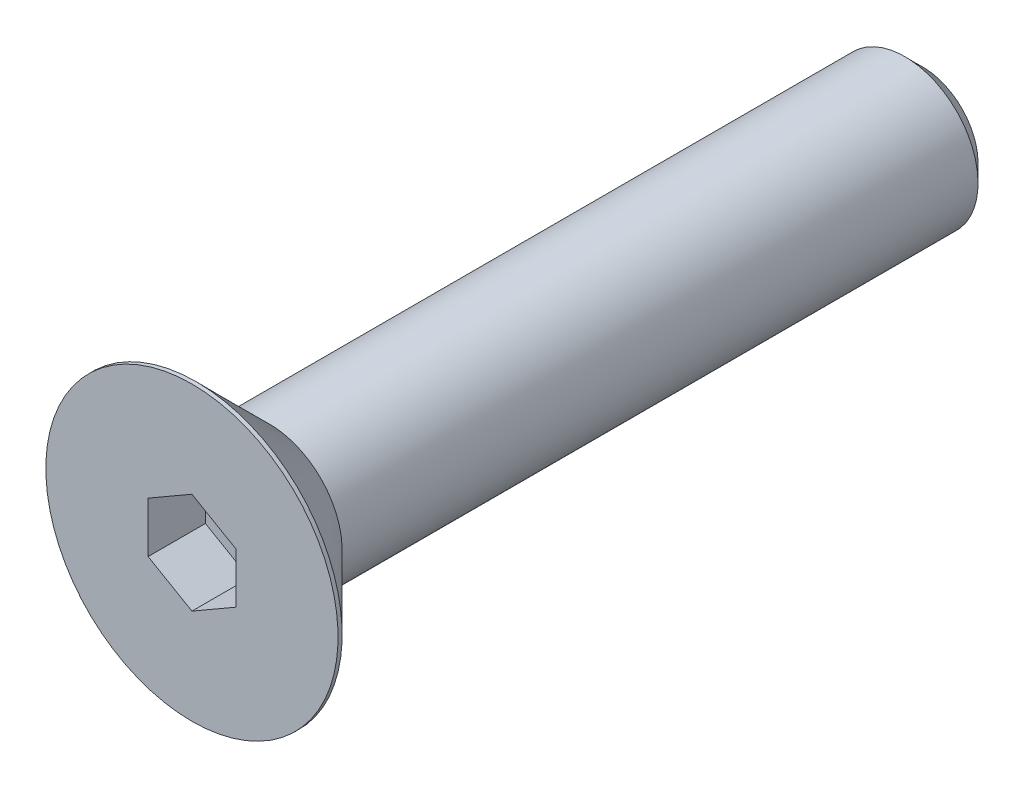
SolidWorks part; units mm, degrees
material "Chrome Stainless Steel"
ref_plane "Front" through (0, 0, 0) normal (0, 0, 1) x (1, 0, 0)
ref_plane "Top" through (0, 0, 0) normal (0, 1, 0) x (1, 0, 0)
ref_plane "Right" through (0, 0, 0) normal (1, 0, 0) x (0, 0, -1)
sketch "Sketch11" plane through (0, 0, 0) normal (1, 0, 0) x (0, 0, -1)
  line L0 (-12.5, 5) -> (12.5, 5) construction
  line L5 (-12.5, 5) -> (-12.5, -5) construction
  line L6 (12.5, 2.5) -> (12.5, -2.5) construction
  line L7 (-12.49, 1.5) -> (-12.49, -1.5) construction
  line L8 (12.45, 2.5866) -> (13.25, 2.5866) construction
  line L9 (13.25, 2.5866) -> (12.85, 1.8938) construction
  line L10 (12.85, 1.8938) -> (12.45, 2.5866) construction
  line L11 (12.8, 1.9804) -> (12.9, 1.9804) construction
  line L12 (12.85, 1.9804) -> (12.85, 1.8938) construction
  line L13 (12.475, 2.5433) -> (13.225, 2.5433) construction
  line L14 (12.85, 2.5866) -> (12.85, 2.5) construction
  line L15 (12.5, 2.5) -> (13.2, 2.5) construction
  line L17 (-12.36, 5) -> (-7.36, 0) construction
  line L18 (-7.36, 0) -> (-12.36, -5) construction
  point P3 (-9.7, 5)
  point P8 (0, 5)
  point P21 (12.85, 2.5433)
  point P26 (-12.5, 0)
  point P28 (-12.49, 0)
  point P29 (12.5, 0)
  dimension "Length" = 25
  dimension "Head Diameter" = 10
  dimension "Thread Major Diameter" = 5
  dimension "Head Height" = 2.8
  dimension "Drive Size" = 3
  dimension "Thread Pitch" = 0.8
  dimension "D1" = 0.1
  dimension "D2" = 0.01
  dimension "D3" = 0.14
  dimension "Countersink Angle" = 90
sketch "Sketch1" plane through (0, 0, 0) normal (1, 0, 0) x (0, 0, -1)
  line L2 (-9.7, 2.5) -> (12.5, 2.5)
  line L3 (12.5, 2.5) -> (12.5, 0)
  line L4 (-10.54, 2.5) -> (-10.54, 0)
  line L5 (-9.7, 2.5) -> (-10.54, 2.5)
  line L6 (-12.5, 5) -> (-12.5, -5) construction
  line L7 (12.5, 2.5) -> (12.5, -2.5) construction
  line L8 (-10.54, 0) -> (12.5, 0)
  dimension "D1" = 1.96
revolve "Revolve1" add sketch "Sketch1" angle 360 mid plane about L8
chamfer "Chamfer1" distance 0.6 angle 45 1 edges at (0, -2.5, -12.5)
sketch "Sketch7" plane through (0, 0, 0) normal (1, 0, 0) x (0, 0, -1)
  line L2 (-12.5, 5) -> (-12.36, 5)
  line L5 (-9.7, 2.34) -> (-9.7, 0)
  line L6 (-12.5, 5) -> (-12.5, 0)
  line L8 (-12.5, 5) -> (-12.5, -5) construction
  line L9 (-12.5, 0) -> (-9.7, 0)
  line L12 (-12.36, 5) -> (-9.7, 2.34)
  line L13 (-12.36, 5) -> (-7.36, 0) construction
revolve "Revolve2" add sketch "Sketch7" angle 360 mid plane about L9 region at (0, 1.9545, 11.2736)
ref_plane "Plane1" through (0, 0, 9.7) normal (0, 0, 1) x (1, 0, 0)
sketch "Sketch5" plane through (0, 0, 12.5) normal (0, 0, 1) x (1, 0, 0)
  line L1 (1.5, -0.866) -> (1.5, 0.866)
  line L2 (1.5, 0.866) -> (0, 1.7321)
  line L3 (0, 1.7321) -> (-1.5, 0.866)
  line L4 (-1.5, 0.866) -> (-1.5, -0.866)
  line L5 (-1.5, -0.866) -> (0, -1.7321)
  line L6 (0, -1.7321) -> (1.5, -0.866)
  circle A0 centre (0, 0) radius 1.5 construction
extrude "Cut-Extrude2" cut sketch "Sketch5" against normal blind 1.96
sketch "Sketch6" plane through (0, 0, 12.5) normal (0, 0, -1) x (-1, 0, 0)
  circle A0 centre (0, 0) radius 1.7321
extrude "Cut-Extrude3" [suppressed] cut sketch "Sketch6" along normal blind 1.96 draft 45
sketch "Sketch12" [suppressed] plane through (0, 0, -12.5) normal (0, 0, -1) x (-1, 0, 0)
  circle A0 centre (0, 0) radius 2.5 construction
  circle A1 centre (0, 0) radius 2.5
curve "Helix/Spiral1" [suppressed] pitch 0.8 height 25 turns 31.25
sketch "Sketch13" [suppressed] plane through (0, 0, 0) normal (1, 0, 0) x (0, 0, -1)
  line L0 (12.475, 2.5433) -> (13.225, 2.5433)
  line L1 (13.225, 2.5433) -> (12.9, 1.9804)
  line L2 (12.9, 1.9804) -> (12.8, 1.9804)
  line L3 (12.8, 1.9804) -> (12.475, 2.5433)
sweep "Cut-Sweep1" [suppressed] cut profiles "Sketch13" path "Helix/Spiral1"
combine bodies "Combine1" [suppressed] operation type add bodies to combine 113 127
equation "\"D1@Chamfer1\"=\"Thread Pitch@Sketch11\" * .75"
equation "\"D1@Cut-Extrude2\"= \"Head Height@Sketch11\" * .7"
equation "\"D1@Cut-Extrude3\" = \"D1@Cut-Extrude2\""
equation "\"D1@Sketch11\"=\"Thread Pitch@Sketch11\"/8"
equation "\"D3@Sketch11\"=\"Head Height@Sketch11\"*.05"
equation "\"D4@Helix/Spiral1\"=\"Thread Pitch@Sketch11\""
equation "\"D1@Sketch1\"=\"Head Height@Sketch11\"*.7"
equation "\"D3@Helix/Spiral1\"=\"Length@Sketch11\""
